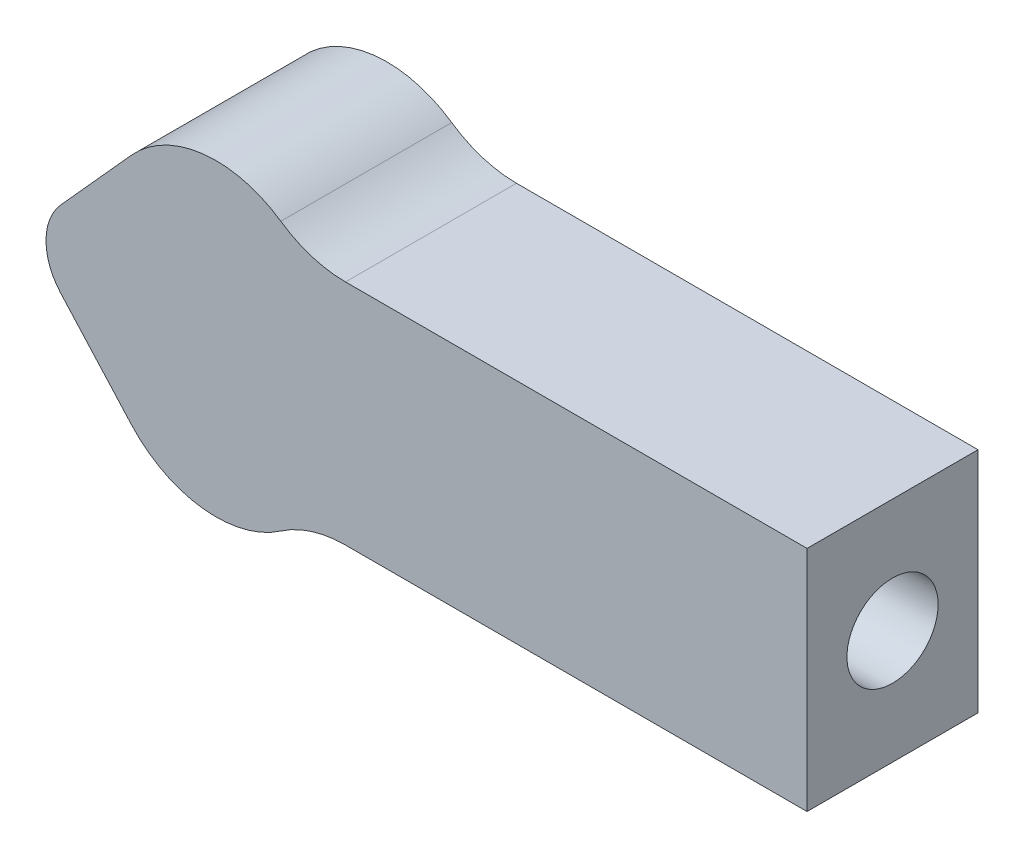
SolidWorks part; units mm, degrees
material "6061-T6 (SS)"
ref_plane "Front Plane" through (0, 0, 0) normal (0, 0, 1) x (1, 0, 0)
ref_plane "Top Plane" through (0, 0, 0) normal (0, 1, 0) x (1, 0, 0)
ref_plane "Right Plane" through (0, 0, 0) normal (1, 0, 0) x (0, 0, -1)
sketch "Sketch1" plane through (0, 0, 0) normal (0, 0, 1) x (1, 0, 0)
  line L0 (-3.05, 4) -> (-6.05, 0.6693)
  line L5 (-4.1825, -2.7426) -> (-3.05, -2) construction
  line L6 (-4.1825, 2.7426) -> (-3.05, 2) construction
  line L7 (-6.05, 0.6693) -> (-3.0711, -2.0138) construction
  line L8 (-6.05, -0.6693) -> (-3.05, -4)
  line L9 (-6.05, -0.6693) -> (-3.0711, 2.0138) construction
  line L10 (7.05, 2) -> (7.05, -2)
  line L15 (-3.05, 2) -> (-3.05, 4)
  line L16 (3.05, -2) -> (-3.05, -2)
  line L17 (-3.05, -2) -> (-3.05, -4)
  line L19 (3.05, 2) -> (-3.05, 2)
  line L21 (3.05, -2) -> (-3.05, 2) construction
  line L22 (3.05, 2) -> (-3.05, -2) construction
  line L23 (3.05, 2) -> (7.05, 2)
  line L25 (3.05, -2) -> (7.05, -2)
  arc A0 (-6.05, 0.6693) -> (-6.05, -0.6693) centre (-5.307, 0) ccw
  point P0 (0, 0)
  point P1 (0, 0)
  dimension "D6" = 4
  dimension "D4" = 1
  dimension "D1" = 6.1
  dimension "D2" = 4
  dimension "D3" = 3
  dimension "D5" = 2
  dimension "D7" = 6.1
extrude "Boss-Extrude1" add sketch "Sketch1" along normal blind 3 contours L8 L0 region at (0.3772, 0, 0)
fillet "Fillet2" radius 2 2 edges at (-3.05, -2, 1.5) (-3.05, 2, 1.5)
fillet "Fillet3" radius 2 2 edges at (-3.05, -4, 1.5) (-3.05, 4, 1.5)
sketch "Sketch2" plane through (7.05, 0, 0) normal (1, 0, 0) x (0, 0, -1)
  line L0 (-3, -2) -> (0, -2) construction
  point P0 (-1.5, 0)
  point P1 (0, 0)
  point P3 (-1.5309, 0)
  point P6 (-1.5, -2)
hole_wizard "M2 Tapped Hole1" positions "Sketch3" profile "Sketch4" tap size "M2" standard "ISO"
sketch "Sketch3" plane through (7.05, 0, 0) normal (1, 0, 0) x (0, 0, -1)
  point P0 (-1.5, 0)
sketch "Sketch4" plane through (7.05, 0, 1.5) normal (0, 1, 0) x (0, 0, -1)
  line L0 (0, 0) -> (0, 4.4807)
  line L1 (0, 4.4807) -> (0.8, 4)
  line L2 (0.8, 4) -> (0.8, 0)
  line L5 (0.8, 0) -> (0, 0)
  line L10 (0, 4.4807) -> (-0.8, 4) construction
  line L11 (0, -6.35) -> (0, 107.95) construction
  dimension "Tap Drill Dia." = 1.6
  dimension "Tap Drill Depth" = 4
  dimension "Drill Angle" = 118
cosmetic thread "Hole Thread1" parameters "D1"=4, "D2"=2
